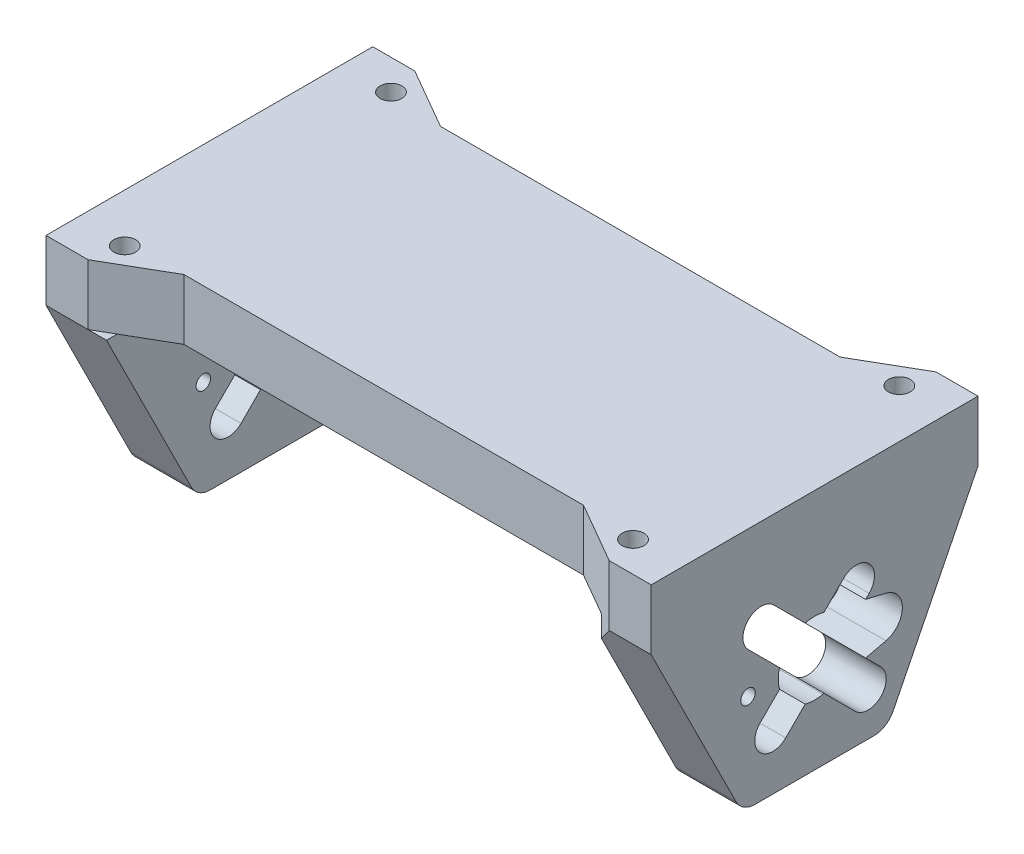
SolidWorks part; units mm, degrees
ref_plane "Front Plane" through (0, 0, 0) normal (0, 0, 1) x (1, 0, 0)
ref_plane "Top Plane" through (0, 0, 0) normal (0, 1, 0) x (1, 0, 0)
ref_plane "Right Plane" through (0, 0, 0) normal (1, 0, 0) x (0, 0, -1)
sketch "Sketch1" plane through (0, 0, 0) normal (0, 1, 0) x (1, 0, 0)
  line L0 (0, 0) -> (9.0185, 0) construction
  line L1 (-42, -22) -> (42, -22) construction
  line L2 (-42, -22) -> (-42, 22) construction
  line L3 (-42, 22) -> (42, 22) construction
  line L4 (42, -22) -> (42, 22) construction
  line L5 (-42, -22) -> (42, 22) construction
  line L6 (-42, 22) -> (42, -22) construction
  line L7 (0, 0) -> (0, 72.303) construction
  line L8 (50, 27) -> (-50, 27)
  line L9 (-50, -25) -> (50, -25)
  line L10 (-50, -25) -> (-50, 25)
  line L11 (-50, 25) -> (50, 25)
  line L12 (50, -25) -> (50, 25)
  line L13 (-50, -25) -> (50, 25) construction
  line L14 (-50, 25) -> (50, -25) construction
  line L15 (58.1438, 20.2) -> (0, 20.2) construction
  line L16 (-33.0144, 21.2) -> (33.0144, 21.2)
  line L17 (33.0144, 21.2) -> (43.0603, 27)
  line L18 (35.2823, 20.2) -> (56.3152, 32.3434) construction
  line L19 (50, 25) -> (50, 27)
  line L20 (-50, 25) -> (-50, 27)
  line L21 (50, -27) -> (-50, -27)
  line L22 (-33.0144, 21.2) -> (-43.0603, 27)
  line L23 (50, -25) -> (50, -27)
  line L25 (33.0144, -21.2) -> (43.0603, -27)
  line L26 (-33.0144, -21.2) -> (33.0144, -21.2)
  line L27 (-33.0144, -21.2) -> (-43.0603, -27)
  line L29 (-50, -25) -> (-50, -27)
  line L30 (0, 21.2) -> (0, 27)
  line L31 (0, -21.2) -> (0, -27)
  circle A0 centre (42, 22) radius 1.8
  circle A1 centre (-42, 22) radius 1.8
  circle A2 centre (-42, -22) radius 1.8
  circle A3 centre (42, -22) radius 1.8
  point P0 (0, 0)
  point P29 (0, 27)
  point P30 (0, 0)
  point P34 (0, 21.2)
  point P41 (0, 0)
  point P42 (0, 25)
  point P43 (0, 27)
  dimension "D3" = 3.6
  dimension "D1" = 44
  dimension "D2" = 84
  dimension "D4" = 8
  dimension "D5" = 3
  dimension "D6" = 1
  dimension "D7" = 30
  dimension "D8" = 2
  dimension "D9" = 2
extrude "Boss-Extrude2" add sketch "Sketch1" along normal blind 10 contours L27 L26 L25 L9 L12 L11 L17 L16 L22 L10 A1 A0 A2 A3 region at (0, 0, 0)
extrude "Boss-Extrude5" add sketch "Sketch1<8>" along normal up to surface (10 mm away) up to face at (-42, 10, -20.2)
sketch "Sketch1<8>" plane through (0, 0, 0) normal (0, 1, 0) x (1, 0, 0) same geometry as "Sketch1"
mirror "Mirror10" about plane through (0, 0, 0) normal (0, 0, 1) of "Boss-Extrude5" second plane through (0, 0, 0) second plane normal (1, 0, 0)
sketch "Sketch2" plane through (0, 0, 0) normal (1, 0, 0) x (0, 0, -1)
  line L0 (0, -30) -> (9.8369, -30)
  line L1 (12, -30) -> (32.3221, 10.6441) construction
  line L2 (0, 0) -> (0, 31.9272) construction
  line L3 (25, 0) -> (-25, 0) construction
  line L4 (-200000, 0) -> (200072.303, 0) construction
  line L5 (27, 0) -> (12.9674, -28.0652)
  arc A0 (9.8369, -30) -> (12.9674, -28.0652) centre (9.8369, -26.5) ccw
  circle A1 centre (0, -14) radius 6
  dimension "D3" = 3.5
  dimension "D4" = 14
  dimension "D5" = 12
  dimension "D1" = 30
  dimension "D2" = 12
sketch "Sketch4" plane through (50, 0, 0) normal (1, 0, 0) x (0, 0, -1)
  line L0 (0, -14) -> (25.7191, -14) construction
  line L1 (27, 0) -> (12.9674, -28.0652) construction
  line L3 (27, 0) -> (12.9674, -28.0652)
  line L4 (-27, 0) -> (27, 0)
  line L5 (27, 0) -> (27, 10)
  line L6 (27, 10) -> (-27, 10)
  line L8 (-27, 0) -> (27, 0)
  line L10 (27, 10) -> (-27, 10)
  line L12 (0, 22.9537) -> (0, -14.1619) construction
  line L13 (0, -14) -> (22.4503, -36.4503) construction
  line L14 (-200000, 0) -> (200072.303, 0) construction
  line L16 (9.8369, -30) -> (-9.8369, -30)
  line L17 (-27, 0) -> (-12.9674, -28.0652)
  line L18 (0, -14) -> (11.6935, -2.3065) construction
  line L19 (-6.8943, -20.8943) -> (6.8943, -7.1057) construction
  line L23 (27, 0) -> (27, 10)
  line L24 (-27, 10) -> (-27, 0)
  line L25 (-27, 10) -> (-27, 0)
  line L26 (-9.0156, -18.773) -> (-5.7956, -15.5529)
  line L27 (-4.773, -23.0156) -> (-1.5529, -19.7956)
  line L28 (-8.8388, -5.1612) -> (8.8388, -22.8388) construction
  line L29 (-6.7175, -3.0398) -> (-1.5529, -8.2044)
  line L30 (-10.9602, -7.2825) -> (-5.7956, -12.4471)
  line L31 (4.2426, -14) -> (10.9602, -20.7175)
  line L32 (1.5529, -8.2044) -> (4.773, -4.9844)
  line L33 (4.2426, -14) -> (9.0156, -9.227)
  line L34 (1.5529, -19.7956) -> (6.7175, -24.9602)
  line L35 (11.7955, -10.5916) -> (1.3636, -8.157)
  line L36 (11.7955, -17.4084) -> (1.3636, -19.843)
  arc A0 (9.8369, -30) -> (12.9674, -28.0652) centre (9.8369, -26.5) ccw construction
  arc A1 (9.8369, -30) -> (12.9674, -28.0652) centre (9.8369, -26.5) ccw
  circle A2 centre (0, -14) radius 6 construction
  circle A3 centre (0, -14) radius 6
  circle A5 centre (11, -14) radius 1.2
  circle A6 centre (8.8388, -22.8388) radius 1.8
  circle A7 centre (-8.8388, -5.1612) radius 1.8
  circle A8 centre (6.8943, -7.1057) radius 1.8
  circle A9 centre (-6.8943, -20.8943) radius 1.8
  arc A10 (-9.8369, -30) -> (-12.9674, -28.0652) centre (-9.8369, -26.5) cw
  circle A11 centre (-11, -14) radius 1.2
  arc A12 (-9.0156, -18.773) -> (-4.773, -23.0156) centre (-6.8943, -20.8943) ccw
  arc A13 (9.0156, -9.227) -> (4.773, -4.9844) centre (6.8943, -7.1057) ccw
  arc A14 (-6.7175, -3.0398) -> (-10.9602, -7.2825) centre (-8.8388, -5.1612) ccw
  arc A15 (6.7175, -24.9602) -> (10.9602, -20.7175) centre (8.8388, -22.8388) ccw
  arc A16 (11.7955, -10.5916) -> (11.7955, -17.4084) centre (11, -14) cw
  point P31 (0, -30)
  point P36 (0, -14)
  point P42 (0, -14)
  point P56 (11.9238, -10.5903)
  point P57 (0, 0)
  point P59 (1.146, -8.1105)
  line M5 (-27, 0) -> (27, 0)
  dimension "D2" = 11
  dimension "D3" = 2.4
  dimension "D5" = 12.5
  dimension "D6" = 3.6
  dimension "D7" = 9.75
  dimension "D8" = 3
  dimension "D9" = 3.5
  dimension "D4" = 45
  dimension "D1" = 0
extrude "Boss-Extrude6" add sketch "Sketch4" against normal blind 10 contours A10 L16 A1 L3 L17 A9 A8 A3 A5 A6 A7 A11 M5 region at (50, -13.7564, -19.4312)
extrude "Cut-Extrude2" cut sketch "Sketch1<11>" against normal through all both and the other way through all contours L30 L11 L17 L8 | L30 L16 L17 L11 region at (20.6762, 0, -26.014) region at (18.2023, 0, -23.1574)
sketch "Sketch1<11>" plane through (0, 0, 0) normal (0, 1, 0) x (1, 0, 0) same geometry as "Sketch1"
mirror "Mirror12" about plane through (0, 0, 0) normal (1, 0, 0) of "Cut-Extrude2" second plane through (0, 0, 0) second plane normal (0, 0, 1)
mirror "Mirror13" about plane through (0, 0, 0) normal (1, 0, 0) of "Boss-Extrude6"
